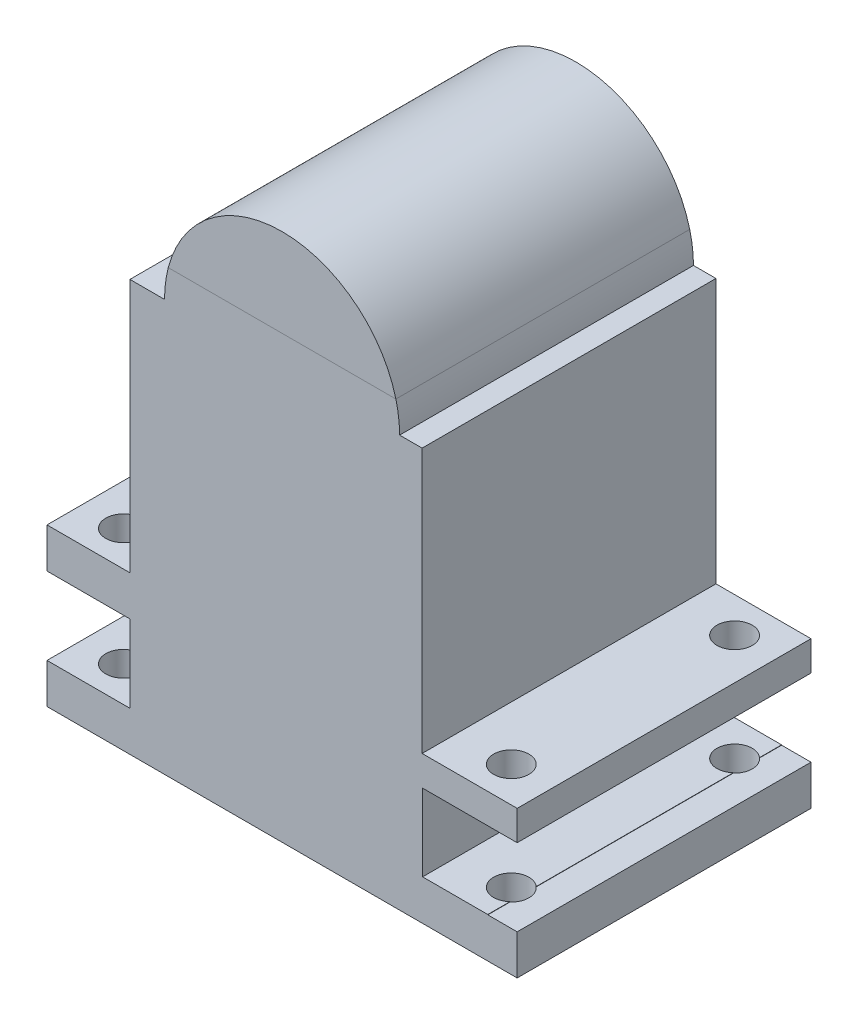
SolidWorks part; units mm, degrees
ref_plane "Plan de face" through (0, 0, 0) normal (0, 0, 1) x (1, 0, 0)
ref_plane "Plan de dessus" through (0, 0, 0) normal (0, 1, 0) x (1, 0, 0)
ref_plane "Plan de droite" through (0, 0, 0) normal (1, 0, 0) x (0, 0, -1)
sketch "Esquisse1" plane through (0, 0, 0) normal (0, 0, 1) x (1, 0, 0)
  line L0 (0, 0) -> (700, 0)
  line L1 (700, 0) -> (700, 450)
  line L2 (700, 450) -> (550, 450)
  line L3 (0, 0) -> (0, 450)
  line L4 (0, 450) -> (150, 450)
  arc A0 (550, 450) -> (150, 450) centre (350, 450) ccw
  dimension "D3" = 200
  dimension "D1" = 700
  dimension "D2" = 450
  dimension "D4" = 150
extrude "Boss.-Extru.1" add sketch "Esquisse1" along normal blind 500
sketch "Esquisse2" plane through (0, 0, 0) normal (0, -1, 0) x (1, 0, 0)
  line L0 (700, 500) -> (700, 0)
  line L1 (700, 0) -> (0, 0)
  line L2 (0, 0) -> (0, 500)
  line L3 (0, 500) -> (700, 500) construction
  line L4 (0, 500) -> (0, 0) construction
  line L5 (0, 500) -> (700, 500)
extrude "Boss.-Extru.2" add sketch "Esquisse2" along normal blind 250
sketch "Esquisse3" plane through (0, 0, 0) normal (0, 0, -1) x (-1, 0, 0)
  circle A0 centre (-287.5, 450) radius 65
extrude "Enlèv. mat.-Extru.1" [suppressed] cut sketch "Esquisse3" against normal blind 500
sketch "Esquisse4" plane through (0, 0, 0) normal (0, 0, -1) x (-1, 0, 0)
  line L0 (0, -50.3189) -> (-91.0727, -50.3189)
  line L1 (0, 450) -> (0, -250) construction
  line L2 (-91.0727, -50.3189) -> (-91.0727, -181.9886)
  line L3 (-91.0727, -181.9886) -> (0, -181.9886)
  line L4 (0, -181.9886) -> (0, -50.3189)
extrude "Enlèv. mat.-Extru.2" cut sketch "Esquisse4" against normal blind 500
sketch "Esquisse5" plane through (0, 0, 0) normal (0, 0, -1) x (-1, 0, 0)
  line L0 (-700, -181.4044) -> (-589.1123, -181.4044)
  line L1 (-700, -250) -> (-700, 450) construction
  line L2 (-589.1123, -181.4044) -> (-589.1123, -50.6587)
  line L3 (-589.1123, -50.6587) -> (-700, -50.6587)
  line L4 (-700, -50.6587) -> (-700, -181.4044)
extrude "Enlèv. mat.-Extru.3" cut sketch "Esquisse5" against normal blind 500
ref_plane "Plan1" through (0, 500, 0) normal (0, -1, 0) x (-1, 0, 0)
sketch "Esquisse6" [suppressed] plane through (0, 0, 500) normal (0, 0, 1) x (1, 0, 0)
  circle A0 centre (287.5, 450) radius 115
  circle A1 centre (287.5, 450) radius 65
extrude "Enlèv. mat.-Extru.4" [suppressed] cut sketch "Esquisse6" against normal blind 100
split "Fractionner2" trim tools "Plan1" bodies to split 105 resulting bodies 109 110
sketch "Esquisse7" [suppressed] plane through (0, 0, 0) normal (0, 0, -1) x (-1, 0, 0)
  circle A0 centre (-287.5, 450) radius 115
  circle A1 centre (-287.5, 450) radius 65
extrude "Enlèv. mat.-Extru.5" [suppressed] cut sketch "Esquisse7" against normal blind 100
sketch "Esquisse9" plane through (0, 0, 500) normal (0, 0, 1) x (1, 0, 0)
  line L1 (700, 450) -> (750, 450)
  line L2 (700, 450) -> (700, -50.6587)
  line L3 (700, -50.6587) -> (750, -50.6587)
  line L4 (750, 450) -> (750, -50.6587)
  line L5 (700, -250) -> (750, -250)
  line L6 (700, -250) -> (700, -181.9464)
  line L7 (700, -181.9464) -> (750, -181.9464)
  line L8 (750, -250) -> (750, -181.9464)
  line L9 (0, -50.3189) -> (-50, -50.3189)
  line L10 (0, -50.3189) -> (0, 450)
  line L11 (0, 450) -> (-50, 450)
  line L12 (-50, -50.3189) -> (-50, 450)
  line L13 (0, -181.9886) -> (-50, -181.9886)
  line L14 (0, -181.9886) -> (0, -250)
  line L15 (0, -250) -> (-50, -250)
  line L16 (-50, -181.9886) -> (-50, -250)
  dimension "D1" = 50
  dimension "D2" = 50
extrude "Boss.-Extru.3" add sketch "Esquisse9" against normal blind 500
sketch "Esquisse10" plane through (0, 0, 500) normal (0, 0, 1) x (1, 0, 0)
  line L0 (91.0727, -50.3189) -> (91.0727, 450)
  line L1 (150, 450) -> (-50, 450) construction
  line L2 (91.0727, 450) -> (-50, 450)
  line L3 (-50, 450) -> (-50, 17.6911)
  line L4 (-50, 450) -> (-50, -50.3189) construction
  line L5 (-50, 17.6911) -> (91.0727, 17.6911)
  line L8 (750, 0) -> (588.2822, 0)
  line L9 (750, -50.6587) -> (750, 450) construction
  line L10 (588.2822, 0) -> (588.2822, 450)
  line L11 (750, 450) -> (550, 450) construction
  line L12 (588.2822, 450) -> (750, 450)
  line L13 (750, 450) -> (750, 0)
  line M3 (150, 450) -> (-50, 450)
  line M4 (-50, 450) -> (-50, -50.3189)
  line M16 (750, -50.6587) -> (750, 450)
  line M17 (750, 450) -> (550, 450)
  dimension "D1" = 68.01
extrude "Enlèv. mat.-Extru.6" cut sketch "Esquisse10" against normal blind 500 contours L10 L8 M16 M17 | L5 L0 M4 M3 region at (20.5364, 233.8456, 500) region at (669.1411, 225, 500)
sketch "Esquisse11" plane through (0, 17.6911, 0) normal (0, 1, 0) x (1, 0, 0)
  line L0 (-50, 0) -> (91.0727, 0) construction
  line L1 (-50, 0) -> (-50, -500) construction
  line L2 (-50, -500) -> (91.0727, -500) construction
  circle A0 centre (20, -60) radius 30
  circle A1 centre (20, -440) radius 30
  dimension "D1" = 60
  dimension "D3" = 70
  dimension "D2" = 70
  dimension "D4" = 60
extrude "Enlèv. mat.-Extru.7" cut sketch "Esquisse11" against normal blind 310
sketch "Esquisse12" plane through (0, 0, 0) normal (0, 1, 0) x (1, 0, 0)
  line L0 (750, 0) -> (588.2822, 0) construction
  line L1 (750, 0) -> (750, -500) construction
  line L2 (750, -500) -> (588.2822, -500) construction
  circle A0 centre (680, -60) radius 30
  circle A1 centre (680, -440) radius 30
  dimension "D3" = 60
  dimension "D4" = 60
  dimension "D1" = 60
  dimension "D2" = 70
extrude "Enlèv. mat.-Extru.8" cut sketch "Esquisse12" against normal blind 310
